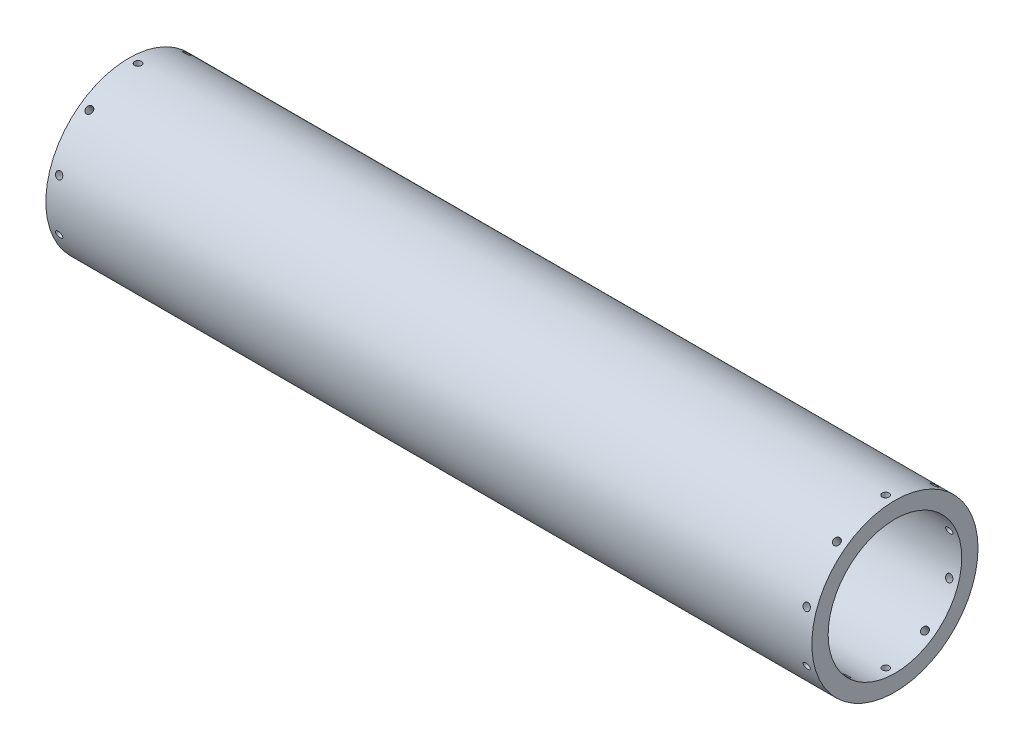
SolidWorks part; units mm, degrees
material "7075-T6 (SN)"
ref_plane "Front Plane" through (0, 0, 0) normal (0, 0, 1) x (1, 0, 0)
ref_plane "Top Plane" through (0, 0, 0) normal (0, 1, 0) x (1, 0, 0)
ref_plane "Right Plane" through (0, 0, 0) normal (1, 0, 0) x (0, 0, -1)
sketch "Sketch1" plane through (0, 0, 0) normal (1, 0, 0) x (0, 0, -1)
  circle A0 centre (0, 0) radius 45.9486
  circle A1 centre (0, 0) radius 57.15
  dimension "D1" = 91.8972
  dimension "D2" = 114.3
extrude "Boss-Extrude1" add sketch "Sketch1" along normal blind 527.05
sketch "Sketch2" plane through (0, 0, 0) normal (-1, 0, 0) x (0, 0, 1)
  circle A0 centre (0, 0) radius 44.577
  circle A1 centre (0, 0) radius 45.9486
  dimension "D1" = 89.154
extrude "Boss-Extrude2" add sketch "Sketch2" against normal blind 88.9
sketch "Sketch4" plane through (0, 0, 0) normal (0, 0, 1) x (1, 0, 0)
  line L0 (0, 0) -> (0, 88.0135) construction
  line L1 (0, 57.15) -> (0, -57.15) construction
  line L2 (0, -62.865) -> (0, 62.865) construction
ref_plane "Plane1" through (0, 57.15, 0) normal (0, 1, 0) x (1, 0, 0)
sketch "Sketch6" plane through (0, 57.15, 0) normal (0, 1, 0) x (1, 0, 0)
  line L0 (0, 57.15) -> (0, -57.15) construction
  circle A0 centre (6.35, 0) radius 2.413
  dimension "D1" = 4.826
  dimension "D2" = 6.35
extrude "Cut-Extrude1" cut sketch "Sketch6" against normal blind 15.24
pattern_circular "CirPattern1" count 10 every 36 about axis through (0, 0, 0) along (-1, 0, 0) of "Cut-Extrude1"
sketch "Sketch7" plane through (0, 57.15, 0) normal (0, 1, 0) x (1, 0, 0)
  line L0 (527.05, -57.15) -> (527.05, 57.15) construction
  circle A0 centre (520.7, 0) radius 2.413
  dimension "D2" = 4.826
  dimension "D1" = 6.35
extrude "Cut-Extrude2" cut sketch "Sketch7" against normal blind 15.24
pattern_circular "CirPattern2" count 10 every 36 about axis through (527.05, 0, 0) along (1, 0, 0) of "Cut-Extrude2"
